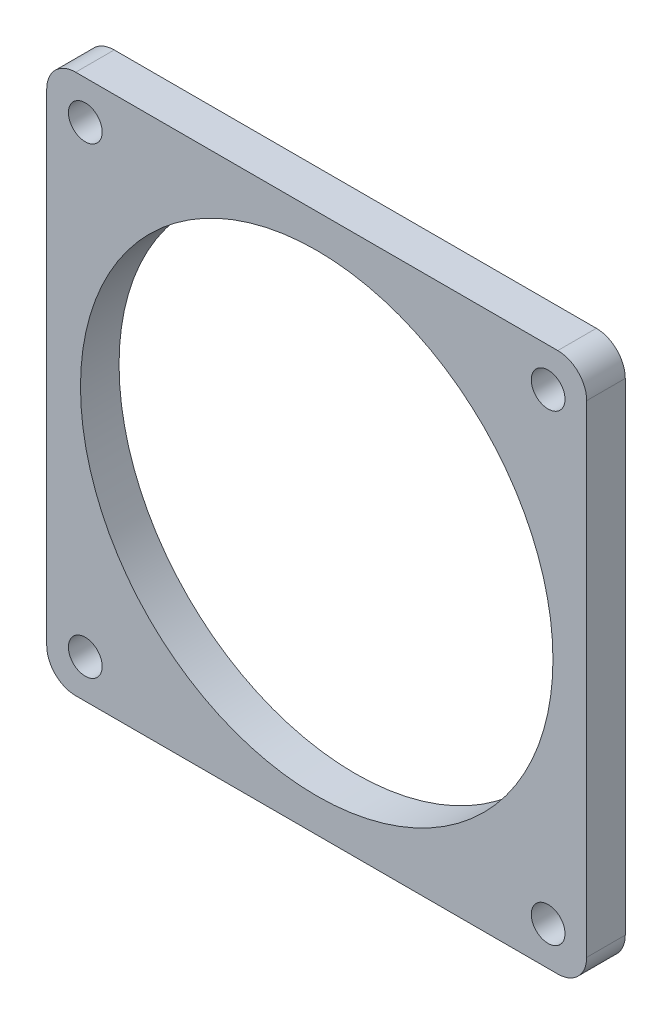
SolidWorks part; units mm, degrees
note: The reader was unsure of these and kept them because the rebuilt part matched: thickness of "Базовая кромка1", "Листовой металл3", "Листовой металл4".
ref_plane "Спереди" through (0, 0, 0) normal (0, 0, 1) x (1, 0, 0)
ref_plane "Сверху" through (0, 0, 0) normal (0, 1, 0) x (1, 0, 0)
ref_plane "Справа" through (0, 0, 0) normal (1, 0, 0) x (0, 0, -1)
other "Configuration Table"
sketch "Эскиз1" plane through (0, 0, 0) normal (0, 0, 1) x (1, 0, 0)
  line L1 (-28, 28) -> (28, 28)
  line L2 (-28, 28) -> (-28, -28)
  line L3 (-28, -28) -> (28, -28)
  line L4 (28, 28) -> (28, -28)
  line L5 (-28, 28) -> (28, -28) construction
  line L6 (-28, -28) -> (28, 28) construction
  point P0 (0, 0)
  dimension "D1" = 56
  dimension "D2" = 56
base flange "Базовая кромка1" sketch "Эскиз1" thickness 4 reverse thickness direction no parameters "D1"=4
sketch "Эскиз6" plane through (0, 0, 0) normal (0, 0, 1) x (1, 0, 0)
  line L0 (-28, -28) -> (28, 28) construction
  circle A0 centre (0, 0) radius 24.5
  circle A1 centre (-24, 24) radius 1.75
  circle A2 centre (24, 24) radius 1.75
  circle A3 centre (24, -24) radius 1.75
  circle A4 centre (-24, -24) radius 1.75
  dimension "D1" = 49
  dimension "D4" = 3.5
  dimension "D2" = 24
  dimension "D3" = 24
  dimension "D7" = 24
  dimension "D8" = 24
  dimension "D5" = 2
  dimension "D6" = 2
extrude "Вырез-Вытянуть1" cut sketch "Эскиз6" against normal blind 4 normal cut yes
fillet "Скругление1" radius 3 4 edges at (-28, 28, -2) (-28, -28, -2) (28, 28, -2) (28, -28, -2)
sketch "Сгиб-Линии1" [suppressed] plane through (0, 0, 0) normal (0, 1, 0) x (1, 0, 0)
sketch "Граничная рамка1" [suppressed] plane through (0, 0, 0) normal (0, 1, 0) x (1, 0, 0)
sheet metal parameters "Листовой металл3" thickness 4 parameters "D1"=3, "D7"=2
flat pattern "Развертка3" [suppressed]
sketch "Сгиб-Линии2" plane through (0, 0, 0) normal (0, 1, 0) x (1, 0, 0)
sketch "Граничная рамка2" [suppressed] plane through (0, 0, 0) normal (0, 1, 0) x (1, 0, 0)
sheet metal parameters "Листовой металл4" thickness 4 parameters "D1"=3, "D7"=2
flat pattern "Развертка3"
sketch "Сгиб-Линии2" plane through (0, 0, 0) normal (0, 1, 0) x (1, 0, 0)
sketch3d "Граничная рамка2" [suppressed]
  line L0 (28, -28, 0) -> (28, 28, 0) construction
  line L1 (-28, -28, 0) -> (-28, 28, 0) construction
  line L2 (28, -28, 0) -> (-28, -28, 0) construction
  line L3 (28, 28, 0) -> (-28, 28, 0) construction
